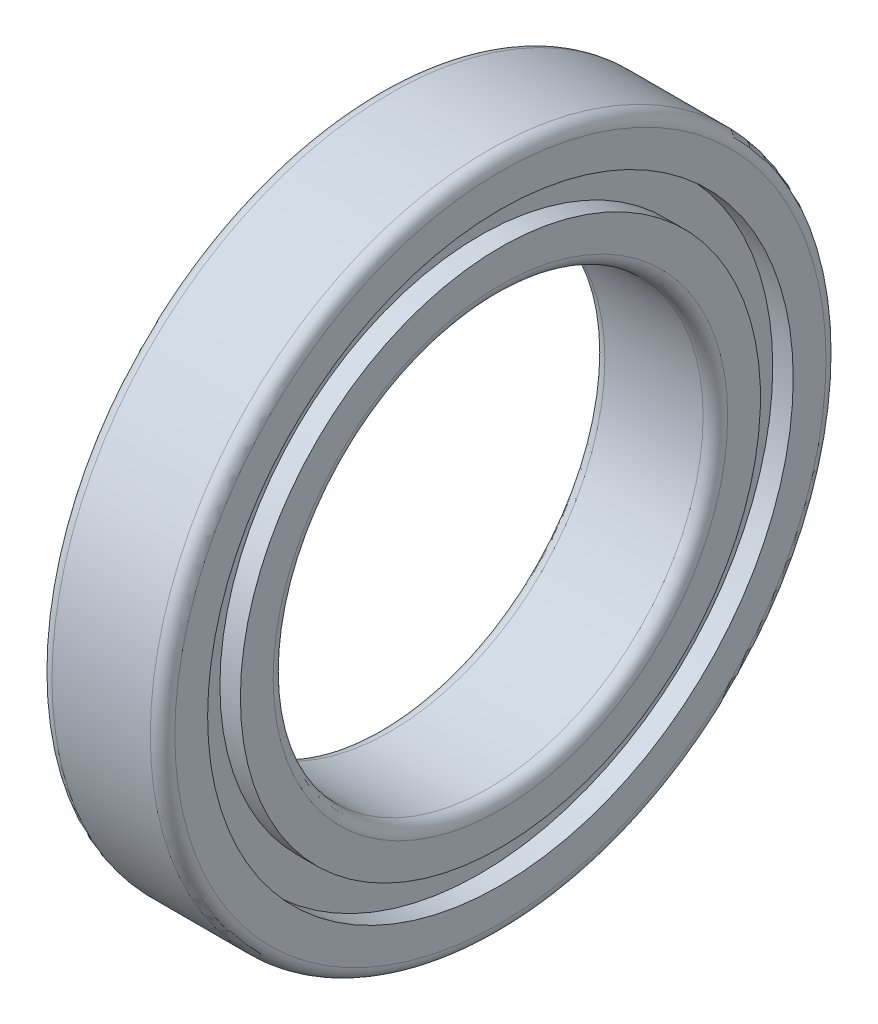
SolidWorks part; units mm, degrees
material "AISI 1020"
ref_plane "Спереди" through (0, 0, 0) normal (0, 0, 1) x (1, 0, 0)
ref_plane "Сверху" through (0, 0, 0) normal (0, 1, 0) x (1, 0, 0)
ref_plane "Справа" through (0, 0, 0) normal (1, 0, 0) x (0, 0, -1)
sketch "Эскиз1" plane through (0, 0, 0) normal (0, 0, 1) x (1, 0, 0)
  line L0 (-1000, 0) -> (49000, 0) construction
  line L1 (0, -1000) -> (0, 49000) construction
  line L2 (4, 17.5) -> (-4, 17.5)
  line L3 (-5, 18.5) -> (-5, 21.1667)
  line L4 (-5, 21.1667) -> (-3.3333, 21.1667)
  line L5 (-3.3333, 21.1667) -> (-3.3333, 23.8333)
  line L6 (-3.3333, 23.8333) -> (-5, 23.8333)
  line L7 (-5, 23.8333) -> (-5, 26.5)
  line L8 (-4, 27.5) -> (4, 27.5)
  line L9 (5, 23.8333) -> (5, 26.5)
  line L10 (3.3333, 23.8333) -> (5, 23.8333)
  line L11 (3.3333, 21.1667) -> (3.3333, 23.8333)
  line L12 (5, 21.1667) -> (3.3333, 21.1667)
  line L13 (5, 18.5) -> (5, 21.1667)
  arc A0 (-4, 17.5) -> (-5, 18.5) centre (-4, 18.5) cw
  arc A1 (-5, 26.5) -> (-4, 27.5) centre (-4, 26.5) cw
  arc A2 (5, 26.5) -> (4, 27.5) centre (4, 26.5) ccw
  arc A3 (4, 17.5) -> (5, 18.5) centre (4, 18.5) ccw
  point P23 (0, 27.5)
  point P27 (0, 17.5)
  dimension "_r" = 1
  dimension "_d" = 35
  dimension "D" = 55
  dimension "B" = 10
  dimension "D2" = 6.6667
revolve "Повернуть1" add sketch "Эскиз1" angle 360 about L0
equation "\"D2@Эскиз1\"= \"B@Эскиз1\" / 3 * 2"
